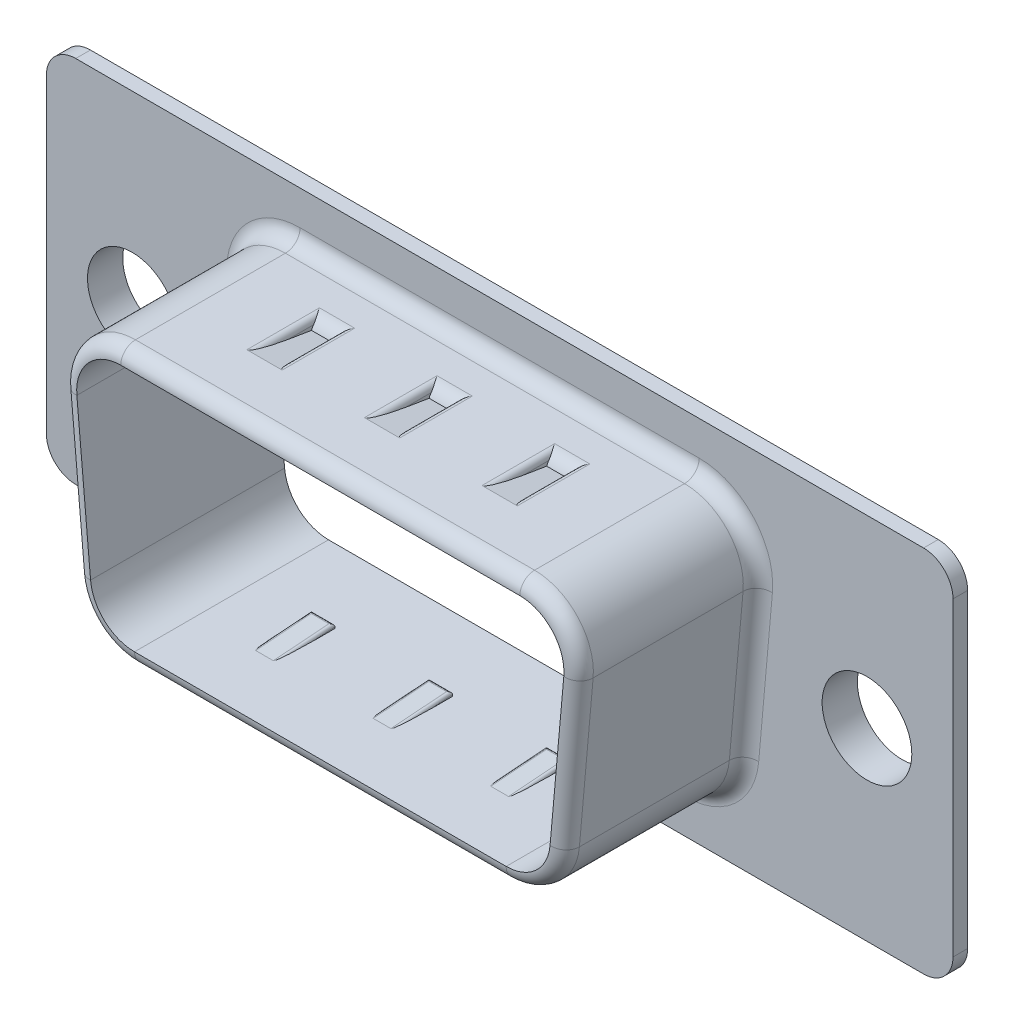
SolidWorks part; units mm, degrees
ref_plane "Front Plane" through (0, 0, 0) normal (0, 0, 1) x (1, 0, 0)
ref_plane "Top Plane" through (0, 0, 0) normal (0, 1, 0) x (1, 0, 0)
ref_plane "Right Plane" through (0, 0, 0) normal (1, 0, 0) x (0, 0, -1)
sketch "Sketch1" plane through (0, 0, 0) normal (0, 0, 1) x (1, 0, 0)
  line L1 (-14.42, 6.275) -> (14.42, 6.275)
  line L2 (-15.42, 5.275) -> (-15.42, -5.275)
  line L3 (-14.42, -6.275) -> (14.42, -6.275)
  line L4 (15.42, 5.275) -> (15.42, -5.275)
  line L5 (0, -6.275) -> (0, 6.275) construction
  line L6 (-15.42, 0) -> (15.42, 0) construction
  arc A0 (14.42, 6.275) -> (15.42, 5.275) centre (14.42, 5.275) cw
  arc A1 (15.42, -5.275) -> (14.42, -6.275) centre (14.42, -5.275) cw
  arc A2 (-15.42, -5.275) -> (-14.42, -6.275) centre (-14.42, -5.275) ccw
  arc A3 (-15.42, 5.275) -> (-14.42, 6.275) centre (-14.42, 5.275) cw
  point P0 (0, 0)
  point P6 (15.42, 6.275)
  point P10 (15.42, -6.275)
  point P15 (-15.42, 6.275)
  dimension "D3" = 1
  dimension "D1" = 30.84
  dimension "D2" = 12.55
extrude "Boss-Extrude1" add sketch "Sketch1" along normal blind 0.5
sketch "Sketch2" plane through (0, 0, 0.5) normal (0, 0, 1) x (1, 0, 0)
  line L0 (-15.42, 0) -> (15.42, 0) construction
  line L1 (-15.42, 5.275) -> (-15.42, -5.275) construction
  line L2 (15.42, -5.275) -> (15.42, 5.275) construction
  circle A0 centre (-12.495, 0) radius 1.525
  circle A1 centre (12.495, 0) radius 1.525
  dimension "D2" = 3.05
  dimension "D3" = 3.05
  dimension "D1" = 2.925
  dimension "D4" = 2.925
  dimension "D5" = 24.99
extrude "Cut-Extrude1" cut sketch "Sketch2" against normal up to surface (0.5 mm away) up to face at (0, 0, 0)
sketch "Sketch3" plane through (0, 0, 0.5) normal (0, 0, 1) x (1, 0, 0)
  line L0 (-15.42, 0) -> (15.42, 0) construction
  line L1 (-15.42, 5.275) -> (-15.42, -5.275) construction
  line L2 (15.42, -5.275) -> (15.42, 5.275) construction
  line L3 (-6.7878, 4.605) -> (6.7878, 4.605)
  line L4 (0, -6.275) -> (0, 6.275) construction
  line L5 (-14.42, -6.275) -> (14.42, -6.275) construction
  line L6 (14.42, 6.275) -> (-14.42, 6.275) construction
  line L7 (-6.3211, -4.605) -> (6.3211, -4.605)
  line L8 (8.975, 4.605) -> (8.975, -3.95) construction
  line L9 (-8.975, 4.605) -> (-8.975, -3.295) construction
  line L10 (8.7799, 2.4266) -> (8.3132, -2.7834)
  line L11 (-8.7799, 2.4266) -> (-8.3132, -2.7834)
  line L12 (-8.975, 4.605) -> (-8.975, 10.7236) construction
  circle A0 centre (-12.495, 0) radius 1.525 construction
  circle A1 centre (12.495, 0) radius 1.525 construction
  arc A2 (8.3132, -2.7834) -> (6.3211, -4.605) centre (6.3211, -2.605) cw
  arc A3 (-6.3211, -4.605) -> (-8.3132, -2.7834) centre (-6.3211, -2.605) cw
  arc A4 (8.7799, 2.4266) -> (6.7878, 4.605) centre (6.7878, 2.605) ccw
  arc A5 (-8.7799, 2.4266) -> (-6.7878, 4.605) centre (-6.7878, 2.605) cw
  point P14 (0, 4.605)
  point P18 (-8.5465, -0.1784)
  point P20 (8.5465, -0.1784)
  point P28 (8.15, -4.605)
  point P31 (-8.15, -4.605)
  dimension "D7" = 2
  dimension "D1" = 4.605
  dimension "D2" = 17.95
  dimension "D3" = 4.605
  dimension "D4" = 16.3
  dimension "D5" = 5.119
  dimension "D6" = 3.9525
  dimension "D8" = 3.9525
extrude "Boss-Extrude2" add sketch "Sketch3" along normal blind 6.1
fillet "Fillet1" radius 0.5 8 edges at (8.2638, 3.9547, 0.5) (8.5465, -0.1784, 0.5) (7.6708, -4.081, 0.5) (0, -4.605, 0.5) (-7.6708, -4.081, 0.5) (-8.5465, -0.1784, 0.5) (-8.2638, 3.9547, 0.5) (0, 4.605, 0.5)
sketch "Sketch4" plane through (0, 0, 6.6) normal (0, 0, 1) x (1, 0, 0)
  line L0 (7.8152, -2.7388) -> (8.2819, 2.4712)
  line L1 (6.7878, 4.105) -> (-6.7878, 4.105)
  line L2 (-8.2819, 2.4712) -> (-7.8152, -2.7388)
  line L3 (-6.3211, -4.105) -> (6.3211, -4.105)
  line L4 (8.3132, -2.7834) -> (8.7799, 2.4266)
  line L5 (6.7878, 4.605) -> (-6.7878, 4.605)
  line L6 (-8.7799, 2.4266) -> (-8.3132, -2.7834)
  line L7 (-6.3211, -4.605) -> (6.3211, -4.605)
  line L8 (8.3132, -2.7834) -> (8.7799, 2.4266) construction
  line L9 (6.7878, 4.605) -> (-6.7878, 4.605) construction
  line L10 (-8.7799, 2.4266) -> (-8.3132, -2.7834) construction
  line L11 (-6.3211, -4.605) -> (6.3211, -4.605) construction
  arc A0 (8.2819, 2.4712) -> (6.7878, 4.105) centre (6.7878, 2.605) ccw
  arc A1 (-6.7878, 4.105) -> (-8.2819, 2.4712) centre (-6.7878, 2.605) ccw
  arc A2 (-7.8152, -2.7388) -> (-6.3211, -4.105) centre (-6.3211, -2.605) ccw
  arc A3 (6.3211, -4.105) -> (7.8152, -2.7388) centre (6.3211, -2.605) ccw
  arc A4 (6.3211, -4.605) -> (8.3132, -2.7834) centre (6.3211, -2.605) ccw
  arc A5 (8.7799, 2.4266) -> (6.7878, 4.605) centre (6.7878, 2.605) ccw
  arc A6 (-6.7878, 4.605) -> (-8.7799, 2.4266) centre (-6.7878, 2.605) ccw
  arc A7 (-8.3132, -2.7834) -> (-6.3211, -4.605) centre (-6.3211, -2.605) ccw
  arc A8 (6.3211, -4.605) -> (8.3132, -2.7834) centre (6.3211, -2.605) ccw construction
  arc A9 (8.7799, 2.4266) -> (6.7878, 4.605) centre (6.7878, 2.605) ccw construction
  arc A10 (-6.7878, 4.605) -> (-8.7799, 2.4266) centre (-6.7878, 2.605) ccw construction
  arc A11 (-8.3132, -2.7834) -> (-6.3211, -4.605) centre (-6.3211, -2.605) ccw construction
  dimension "D1" = 0
  dimension "D2" = 0.5
extrude "Cut-Extrude2" cut sketch "Sketch4" against normal up to surface (6.6 mm away) up to face at (10.97, 0, 0)
fillet "Fillet2" radius 0.5 8 edges at (7.6708, -4.081, 6.6) (0, -4.605, 6.6) (-7.6708, -4.081, 6.6) (-8.5465, -0.1784, 6.6) (-8.2638, 3.9547, 6.6) (0, 4.605, 6.6) (8.2638, 3.9547, 6.6) (8.5465, -0.1784, 6.6)
sketch "Sketch8" plane through (0, 0, 0) normal (1, 0, 0) x (0, 0, -1)
  line L0 (-0.5, 5.105) -> (-2.5, 5.105) construction
  line L1 (-2.5, 5.105) -> (-2.5, 4.605) construction
  line L2 (-6.1, 4.605) -> (-1, 4.605) construction
  line L3 (-2.5, 4.605) -> (-4.5, 4.605) construction
  line L4 (-4.5, 4.605) -> (-2.5, 4.275)
  line L5 (-2.5, 4.275) -> (-2.5, 4.605)
  line L6 (-2.5, 4.605) -> (-4.5, 4.605)
  dimension "D1" = 2
  dimension "D2" = 2
  dimension "D3" = 0.33
extrude "Cut-Extrude3" cut sketch "Sketch8" against normal mid plane 0.8
pattern_linear "LPattern1" count 2 spacing 4 along (1, 0, 0) of "Cut-Extrude3"
pattern_linear "LPattern2" count 2 spacing 4 along (-1, 0, 0) of "Cut-Extrude3"
fillet "Fillet3" radius 0.5 3 edges at (4, 4.605, 2.5) (0, 4.605, 2.5) (-4, 4.605, 2.5)
mirror "Mirror1" about plane through (0, 0, 0) normal (0, 1, 0) of "Cut-Extrude3", "LPattern2", "LPattern1"
fillet "Fillet4" radius 0.2 12 edges at (-4.4, -4.605, 3.5) (-3.6, -4.605, 3.5) (-0.4, -4.605, 3.5) (0.4, -4.605, 3.5) (3.6, -4.605, 3.5) (4.4, -4.605, 3.5) (-4.4, 4.605, 3.2649) (-3.6, 4.605, 3.2649) (-0.4, 4.605, 3.2649) (0.4, 4.605, 3.2649) (3.6, 4.605, 3.2649) (4.4, 4.605, 3.2649)
sketch "Sketch9" plane through (0, 0, 0) normal (0, 0, -1) x (-1, 0, 0)
  line L0 (-14.02, 0) -> (-14.32, 0) construction
  circle A0 centre (-12.495, 0) radius 1.525 construction
  circle A1 centre (-12.495, 0) radius 1.525
  circle A2 centre (12.495, 0) radius 1.525 construction
  circle A3 centre (12.495, 0) radius 1.525
  circle A4 centre (-12.495, 0) radius 1.825
  circle A5 centre (12.495, 0) radius 1.825
  dimension "D1" = 3.05
  dimension "D3" = 3.65
  dimension "D4" = 3.65
  dimension "D2" = 0.3
extrude "Boss-Extrude3" add sketch "Sketch9" along normal blind 0.5
sketch "Sketch10" plane through (0, 0, -0.5) normal (0, 0, -1) x (-1, 0, 0)
  line L0 (-14.02, 0) -> (-14.52, 0) construction
  circle A0 centre (-12.495, 0) radius 1.525 construction
  circle A1 centre (-12.495, 0) radius 1.525
  circle A2 centre (12.495, 0) radius 1.525 construction
  circle A3 centre (12.495, 0) radius 1.525
  circle A4 centre (-12.495, 0) radius 2.025
  circle A5 centre (12.495, 0) radius 2.025
  dimension "D2" = 4.05
  dimension "D3" = 4.05
  dimension "D1" = 0.5
extrude "Boss-Extrude4" add sketch "Sketch10" along normal blind 0.2
sketch "Sketch13" plane through (0, 0, 0) normal (1, 0, 0) x (0, 0, -1)
  line L5 (-0.5, 5.105) -> (-2.5, 5.105) construction
  line L6 (-2.5, 5.105) -> (-2.5, 4.605) construction
  line L7 (-6.1, 4.605) -> (-1, 4.605) construction
  line L8 (-2.5, 4.605) -> (-2.5, 4.105) construction
  line L9 (-2.5, 4.105) -> (-4.5, 4.105)
  line L10 (-4.5, 4.105) -> (-2.5, 3.955)
  line L11 (-2.5, 3.955) -> (-2.5, 4.105)
  dimension "D3" = 2
  dimension "D4" = 0.5
  dimension "D5" = 2
  dimension "D6" = 0.15
extrude "Boss-Extrude5" add sketch "Sketch13" along normal mid plane 0.8
pattern_linear "LPattern3" count 2 spacing 4 along (-1, 0, 0) of "Boss-Extrude5"
pattern_linear "LPattern4" count 2 spacing 4 along (1, 0, 0) of "Boss-Extrude5"
mirror "Mirror2" about plane through (0, 0, 0) normal (0, 1, 0) of "LPattern3", "Boss-Extrude5", "LPattern4"
fillet "Fillet7" radius 0.1 18 edges at (-4, 3.955, 2.5) (-3.6, 4.03, 3.5) (-4.4, 4.03, 3.5) (0, 3.955, 2.5) (-0.4, 4.03, 3.5) (0.4, 4.03, 3.5) (4.4, 4.03, 3.5) (4, 3.955, 2.5) (3.6, 4.03, 3.5) (4.4, -4.03, 3.5) (4, -3.955, 2.5) (3.6, -4.03, 3.5) (0, -3.955, 2.5) (0.4, -4.03, 3.5) (-0.4, -4.03, 3.5) (-4, -3.955, 2.5) (-4.4, -4.03, 3.5) (-3.6, -4.03, 3.5)
